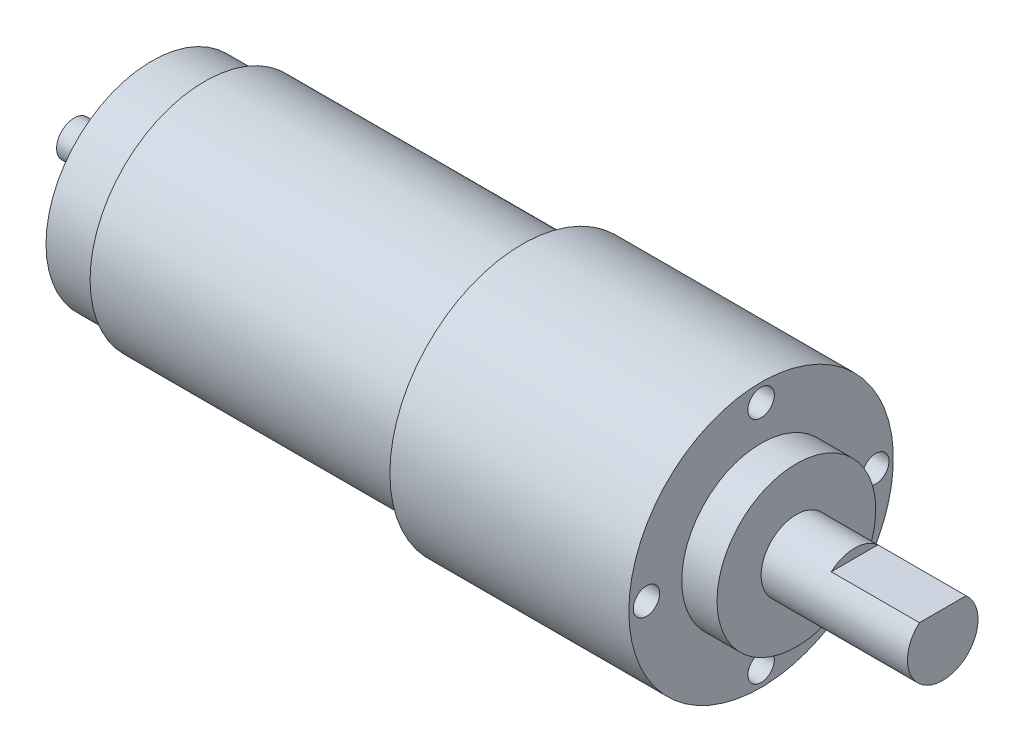
SolidWorks part; units mm, degrees
ref_plane "Plan de face" through (0, 0, 0) normal (0, 0, 1) x (1, 0, 0)
ref_plane "Plan de dessus" through (0, 0, 0) normal (0, 1, 0) x (1, 0, 0)
ref_plane "Plan de droite" through (0, 0, 0) normal (1, 0, 0) x (0, 0, -1)
ref_axis "Axe1" through (-5.325, 0, 0) along (1, 0, 0)
sketch "Esquisse1" plane through (0, 0, 0) normal (0, 0, 1) x (1, 0, 0)
  line L0 (0, 0) -> (98.5, 0)
  line L1 (98.5, 0) -> (98.5, 4)
  line L2 (98.5, 4) -> (81.9, 4)
  line L3 (81.9, 4) -> (81.9, 9)
  line L4 (81.9, 9) -> (77.9, 9)
  line L5 (77.9, 9) -> (77.9, 15)
  line L6 (77.9, 15) -> (50.8, 15)
  line L7 (50.8, 15) -> (50.8, 13)
  line L8 (50.8, 13) -> (14.8, 13)
  line L9 (14.8, 13) -> (14.8, 12)
  line L10 (14.8, 12) -> (8.8, 12)
  line L11 (8.8, 12) -> (8.8, 2)
  line L12 (8.8, 2) -> (0, 2)
  line L13 (0, 2) -> (0, 0)
  dimension "D1" = 27.1
  dimension "D2" = 4
  dimension "D3" = 20.6
  dimension "D4" = 13
  dimension "D5" = 15
  dimension "D6" = 9
  dimension "D7" = 12
  dimension "D8" = 2
  dimension "D9" = 42
  dimension "D10" = 6
  dimension "D11" = 8.8
  dimension "D12" = 4
  dimension "D13" = 98.5
revolve "MainRevolution" add sketch "Esquisse1" angle 360 about L0
sketch "Esquisse2" plane through (98.5, 0, 0) normal (1, 0, 0) x (0, 0, -1)
  line L1 (-2.6458, 3) -> (2.6458, 3)
  line L2 (-2.6458, 3) -> (-2.6458, 4)
  line L3 (-2.6458, 4) -> (2.6458, 4)
  line L4 (2.6458, 3) -> (2.6458, 4)
  circle A0 centre (0, 0) radius 4 construction
  circle A1 centre (0, 0) radius 4 construction
  dimension "D1" = 1
extrude "Enlèv. mat.-Extru.1" cut sketch "Esquisse2" against normal blind 10
sketch "Esquisse3" plane through (77.9, 0, 0) normal (1, 0, 0) x (0, 0, -1)
  line L0 (0, 8.8) -> (0, -8.8) construction
  circle A0 centre (0, 13) radius 1.5
  circle A1 centre (0, 0) radius 15 construction
  dimension "D1" = 3
  dimension "D2" = 13
extrude "FixHoles" cut sketch "Esquisse3" against normal blind 3
pattern_circular "RepeatFixHoles" count 4 every 90 about axis through (-5.325, 0, 0) along (1, 0, 0) of "FixHoles"
